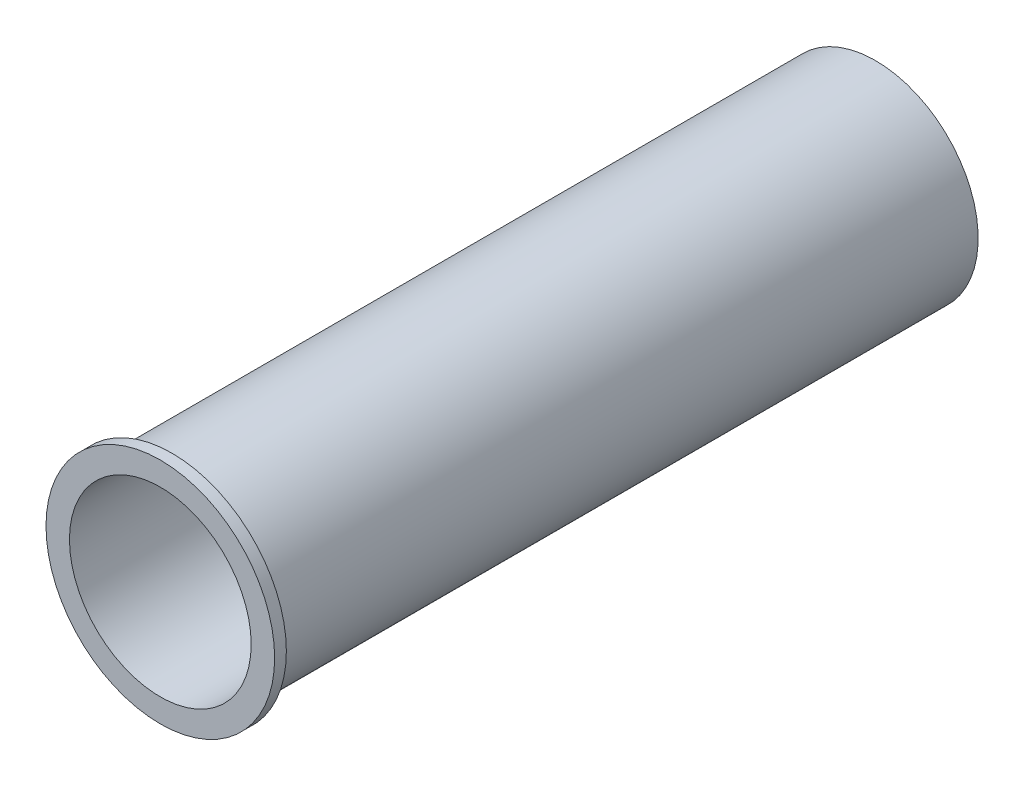
SolidWorks part; units mm, degrees
ref_plane "Alzado" through (0, 0, 0) normal (1, 0, 0) x (0, 1, 0)
ref_plane "Planta" through (0, 0, 0) normal (0, 0, 1) x (0, 1, 0)
ref_plane "Vista lateral" through (0, 0, 0) normal (0, 1, 0) x (-1, 0, 0)
sketch "Croquis1" plane through (0, 0, 0) normal (1, 0, 0) x (0, 1, 0)
  line L0 (15.5, -60) -> (15.5, 60)
  line L1 (15.5, 60) -> (19.5, 60)
  line L2 (19.5, 60) -> (19.5, 58)
  line L3 (19.5, 58) -> (17.5, 58)
  line L4 (17.5, 58) -> (17.5, -62)
  line L5 (17.5, -62) -> (14, -62)
  line L6 (14, -62) -> (14, -60)
  line L7 (14, -60) -> (15.5, -60)
  line L8 (0, 0) -> (0, 4.1277) construction
  point P3 (15.5, 0)
  dimension "D1" = 2
  dimension "D2" = 1.5
  dimension "D3" = 2
  dimension "D4" = 2
  dimension "D5" = 2
  dimension "D7" = 120
  dimension "D6" = 31
revolve "Revolución1" add sketch "Croquis1" angle 360 about L8
equation "\"D4@Croquis1\"=\"D3@Croquis1\""
equation "\"D5@Croquis1\"=\"D3@Croquis1\""
